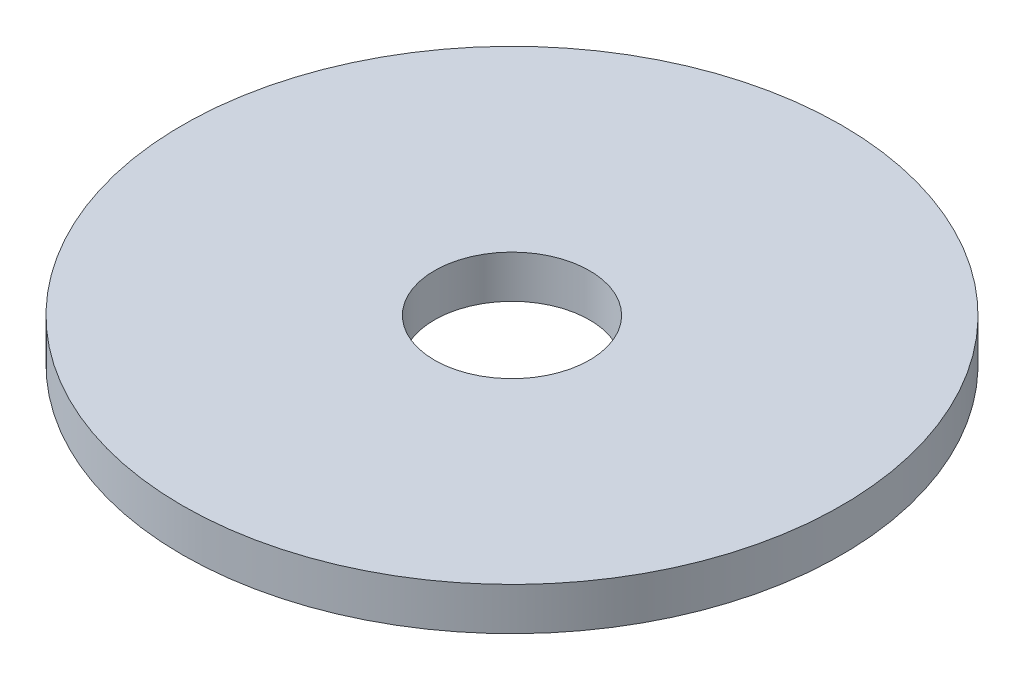
SolidWorks part; units mm, degrees
ref_plane "Front Plane" through (0, 0, 0) normal (0, 0, 1) x (1, 0, 0)
ref_plane "Top Plane" through (0, 0, 0) normal (0, 1, 0) x (1, 0, 0)
ref_plane "Right Plane" through (0, 0, 0) normal (1, 0, 0) x (0, 0, -1)
sketch "Sketch1" plane through (0, 0, 0) normal (0, 1, 0) x (1, 0, 0)
  circle A0 centre (0, 0) radius 85
  dimension "FLANGE_OD" = 170
extrude "Boss-Extrude1" add sketch "Sketch1" along normal blind 11
sketch "Sketch2" plane through (0, 0, 0) normal (0, 1, 0) x (1, 0, 0)
  circle A0 centre (0, 0) radius 20
  dimension "BORE_D" = 40
extrude "Cut-Extrude1" cut sketch "Sketch2" along normal through all
sketch "Sketch3" plane through (0, 11, 0) normal (0, 1, 0) x (1, 0, 0)
  circle A0 centre (0, 0) radius 12.5278 construction
  circle A1 centre (-12.5278, 0) radius 3.9868
  dimension "BOLT_D" = 7.9736
  dimension "BOLT_PCD" = 25.0556
extrude "Cut-Extrude2" cut sketch "Sketch3" against normal blind 10.7219 rebuild error yes
pattern_circular "CirPattern1" count 5 over 360 rebuild error yes
